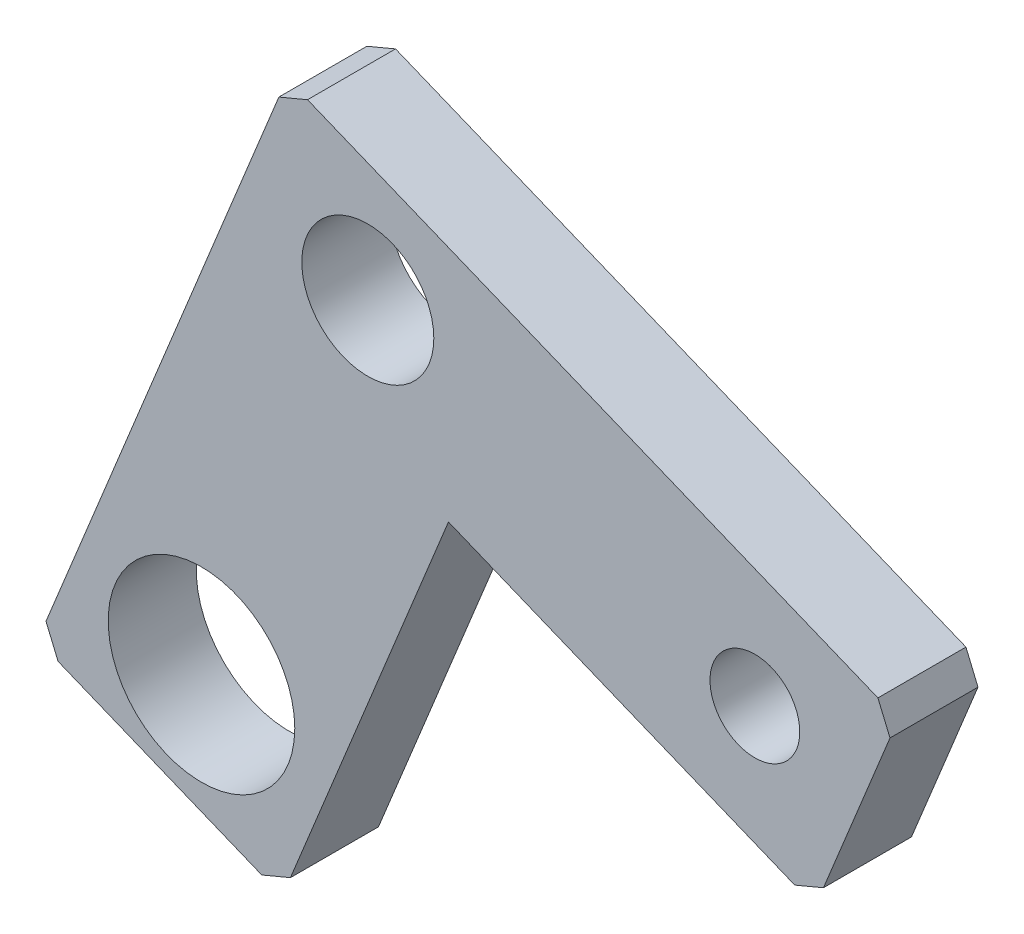
SolidWorks part; units mm, degrees
ref_plane "前基準面" through (0, 0, 0) normal (0, 0, 1) x (1, 0, 0)
ref_plane "上基準面" through (0, 0, 0) normal (0, 1, 0) x (1, 0, 0)
ref_plane "右基準面" through (0, 0, 0) normal (1, 0, 0) x (0, 0, -1)
sketch "草圖1" plane through (0, 0, 0) normal (0, 0, 1) x (1, 0, 0)
  line L0 (-42.6847, 14.9509) -> (26.7532, -13.3931)
  line L5 (26.7532, -13.3931) -> (17.3052, -36.5391)
  line L6 (17.3052, -36.5391) -> (-24.3576, -19.5327)
  line L7 (-24.3576, -19.5327) -> (-43.2535, -65.8246)
  line L8 (-43.2535, -65.8246) -> (-71.0287, -54.487)
  line L9 (-71.0287, -54.487) -> (-42.6847, 14.9509)
  line L10 (22.0292, -24.9661) -> (-47.4087, 3.3779) construction
  line L11 (-57.1411, -60.1558) -> (-28.7971, 9.2821) construction
  circle A0 centre (10.4562, -20.2421) radius 5.1
  circle A1 centre (-33.5211, -2.2909) radius 7.5
  circle A2 centre (-52.4171, -48.5828) radius 10.6
  point P12 (-33.5211, -2.2909)
  dimension "D5" = 10.2
  dimension "D8" = 15
  dimension "D9" = 21.2
  dimension "D1" = 25
  dimension "D2" = 30
  dimension "D3" = 75
  dimension "D4" = 75
  dimension "D6" = 12.5
  dimension "D7" = 12.5
  dimension "D10" = 12.5
extrude "填料-伸長1" add sketch "草圖1" against normal blind 10
chamfer "導角1" distance 2.5 angle 45 5 edges at (-43.2535, -65.8246, -5) (17.3052, -36.5391, -5) (26.7532, -13.3931, -5) (-71.0287, -54.487, -5) (-42.6847, 14.9509, -5)
